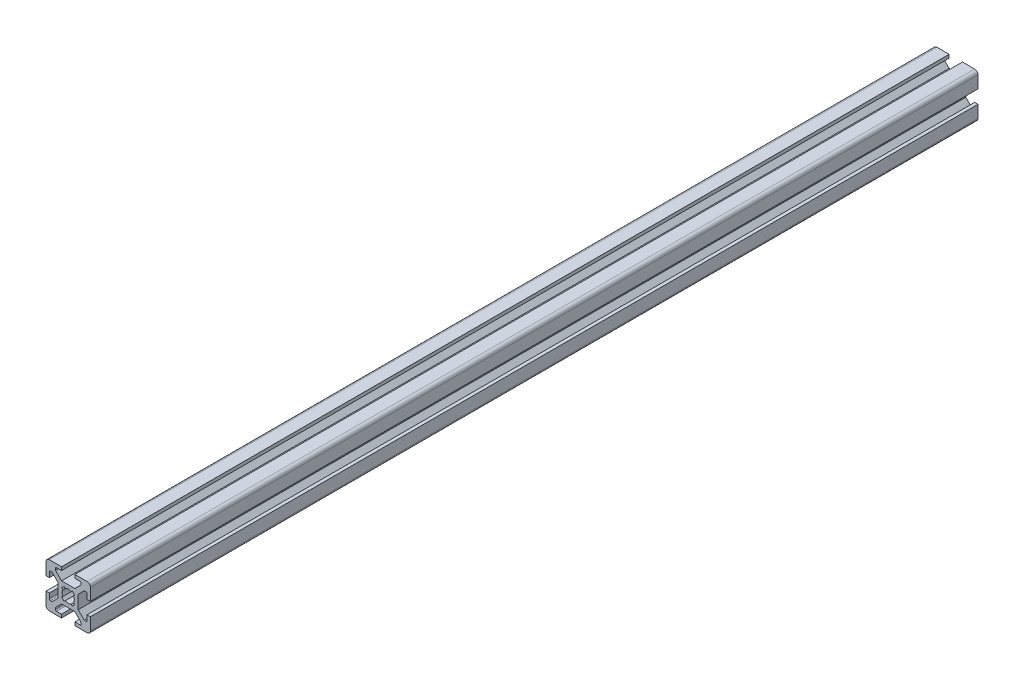
SolidWorks part; units mm, degrees
ref_plane "Alzado" through (0, 0, 0) normal (0, 0, 1) x (1, 0, 0)
ref_plane "Planta" through (0, 0, 0) normal (0, 1, 0) x (1, 0, 0)
ref_plane "Vista lateral" through (0, 0, 0) normal (1, 0, 0) x (0, 0, -1)
other "Tabla de configuración"
sketch "Croquis1" plane through (0, 0, 0) normal (0, 0, 1) x (1, 0, 0)
  line L0 (3, -4.5) -> (5.7414, -7.2414)
  line L1 (-10, 10) -> (-3, 10)
  line L2 (-10, 10) -> (-10, 3)
  line L3 (-10, -10) -> (-3, -10)
  line L4 (10, 10) -> (10, 3)
  line L5 (-10, 10) -> (10, -10) construction
  line L6 (-10, -10) -> (10, 10) construction
  line L7 (-3, 4.5) -> (3, 4.5)
  line L8 (-4.5, 3) -> (-4.5, -3)
  line L9 (-3, -4.5) -> (3, -4.5)
  line L10 (4.5, 3) -> (4.5, -3)
  line L11 (-4.5, 4.5) -> (4.5, -4.5) construction
  line L12 (-4.5, -4.5) -> (4.5, 4.5) construction
  line L13 (5.7414, -7.2414) -> (5.7414, -8.5)
  line L14 (5.7414, -8.5) -> (3, -8.5)
  line L15 (3, -8.5) -> (3, -10)
  line L16 (-7.2414, 5.7414) -> (-4.5, 3)
  line L17 (-3, -10) -> (-3, -8.5)
  line L18 (-3, -8.5) -> (-5.7414, -8.5)
  line L19 (-5.7414, -8.5) -> (-5.7414, -7.2414)
  line L20 (-5.7414, -7.2414) -> (-3, -4.5)
  line L21 (0, -4.5) -> (0, -10) construction
  line L22 (3, -10) -> (10, -10)
  line L24 (-4.5, -3) -> (-7.2414, -5.7414)
  line L25 (-7.2414, -5.7414) -> (-8.5, -5.7414)
  line L26 (-8.5, -5.7414) -> (-8.5, -3)
  line L27 (-8.5, -3) -> (-10, -3)
  line L28 (-10, 3) -> (-8.5, 3)
  line L29 (-8.5, 3) -> (-8.5, 5.7414)
  line L30 (-8.5, 5.7414) -> (-7.2414, 5.7414)
  line L31 (5.7414, 7.2414) -> (3, 4.5)
  line L33 (-3, 4.5) -> (-5.7414, 7.2414)
  line L34 (-5.7414, 7.2414) -> (-5.7414, 8.5)
  line L35 (-5.7414, 8.5) -> (-3, 8.5)
  line L36 (-3, 8.5) -> (-3, 10)
  line L37 (3, 10) -> (3, 8.5)
  line L38 (3, 8.5) -> (5.7414, 8.5)
  line L39 (5.7414, 8.5) -> (5.7414, 7.2414)
  line L40 (7.2414, -5.7414) -> (4.5, -3)
  line L42 (4.5, 3) -> (7.2414, 5.7414)
  line L43 (7.2414, 5.7414) -> (8.5, 5.7414)
  line L44 (8.5, 5.7414) -> (8.5, 3)
  line L45 (8.5, 3) -> (10, 3)
  line L46 (10, -3) -> (8.5, -3)
  line L47 (8.5, -3) -> (8.5, -5.7414)
  line L48 (8.5, -5.7414) -> (7.2414, -5.7414)
  line L49 (3, 10) -> (10, 10)
  line L50 (-10, -3) -> (-10, -10)
  line L51 (10, -3) -> (10, -10)
  line L52 (3, 4.5) -> (-3, 4.5) [skipped]
  line L53 (-4.5, 3) -> (-4.5, -3) [skipped]
  line L54 (4.5, -3) -> (4.5, 3) [skipped]
  point P0 (0, 0)
  point P6 (0, 0)
  point P26 (0, 0)
  point P37 (0, 0)
  point P48 (0, 0)
  point P59 (0, 0)
  dimension "D1" = 20
  dimension "D2" = 1.5
  dimension "D3" = 9
  dimension "D4" = 7
  dimension "D5" = 6
  dimension "D6" = 4
  dimension "D7" = 5.5
extrude "Saliente-Extruir1" add sketch "Croquis1" along normal blind 400
fillet "Redondeo1" radius 1.5 4 edges at (10, -10, 200) (-10, -10, 200) (10, 10, 200) (-10, 10, 200)
fillet "Redondeo2" radius 0.5 7 edges at (-5.7414, -8.5, 200) (5.7414, 8.5, 200) (-5.7414, 8.5, 200) (8.5, -5.7414, 200) (-8.5, -5.7414, 200) (8.5, 5.7414, 200) (-8.5, 5.7414, 200)
sketch "Croquis2" plane through (0, 0, 0) normal (0, 0, -1) x (-1, 0, 0)
  line L0 (-1.3405, 2.4012) -> (-1.8708, 2.9315)
  line L1 (-1.8708, 2.9315) -> (-2.9315, 1.8708)
  line L2 (-2.9315, 1.8708) -> (-2.4012, 1.3405)
  line L3 (-4.5, 3) -> (-7.2414, 5.7414) construction
  line L5 (1.8708, 2.9315) -> (1.3405, 2.4012)
  line L6 (2.9315, 1.8708) -> (1.8708, 2.9315)
  line L7 (2.4012, 1.3405) -> (2.9315, 1.8708)
  line L8 (2.9315, -1.8708) -> (2.4012, -1.3405)
  line L9 (1.8708, -2.9315) -> (2.9315, -1.8708)
  line L10 (1.3405, -2.4012) -> (1.8708, -2.9315)
  line L11 (-1.8708, -2.9315) -> (-1.3405, -2.4012)
  line L12 (-2.9315, -1.8708) -> (-1.8708, -2.9315)
  line L13 (-2.4012, -1.3405) -> (-2.9315, -1.8708)
  arc A0 (-2.4012, 1.3405) -> (-2.4012, -1.3405) centre (0, 0) ccw
  arc A1 (-1.3405, -2.4012) -> (1.3405, -2.4012) centre (0, 0) ccw
  arc A2 (2.4012, -1.3405) -> (2.4012, 1.3405) centre (0, 0) ccw
  arc A3 (1.3405, 2.4012) -> (-1.3405, 2.4012) centre (0, 0) ccw
  point P25 (0, 0)
  dimension "D1" = 5.5
  dimension "D2" = 0.75
  dimension "D3" = 1.5
  dimension "D4" = 4
extrude "Cortar-Extruir1" cut sketch "Croquis2" against normal through all
